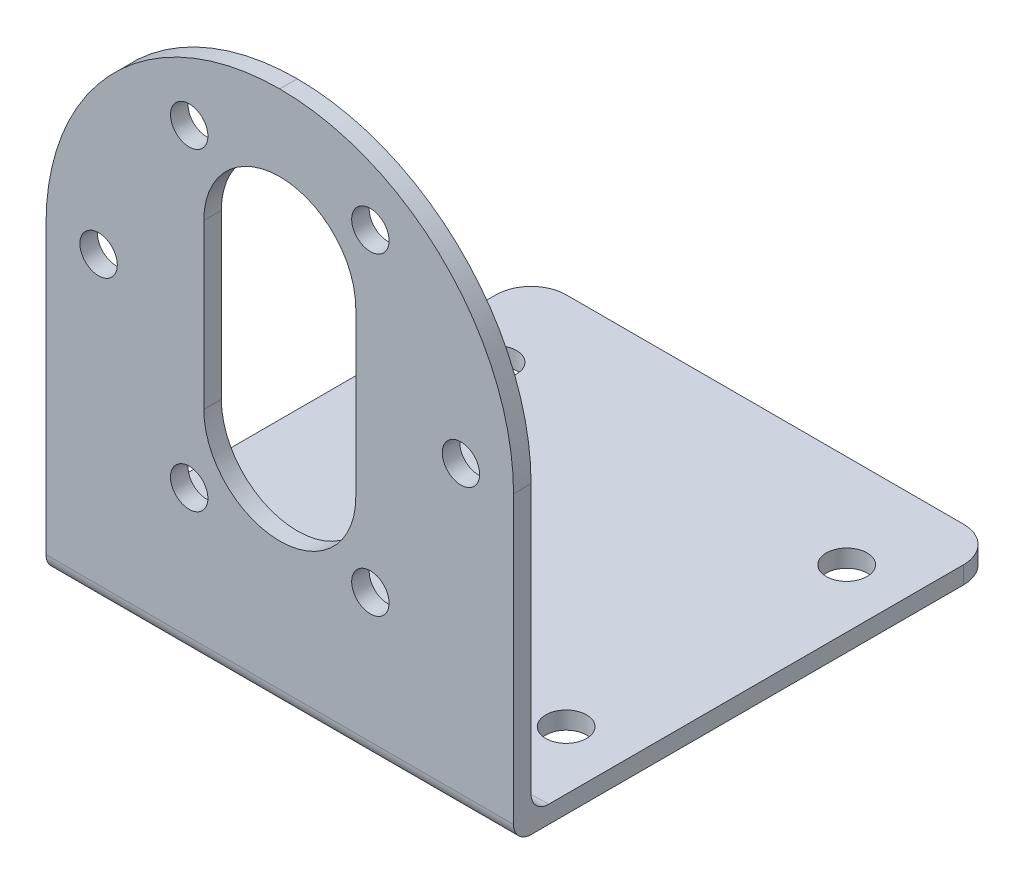
SolidWorks part; units mm, degrees
material "AISI 304"
ref_plane "前视基准面" through (0, 0, 0) normal (0, 0, 1) x (1, 0, 0)
ref_plane "上视基准面" through (0, 0, 0) normal (0, 1, 0) x (1, 0, 0)
ref_plane "右视基准面" through (0, 0, 0) normal (1, 0, 0) x (0, 0, -1)
sketch "Sketch1" plane through (0, 0, 0) normal (1, 0, 0) x (0, 0, -1)
  line L0 (0, 0) -> (40, 0)
  line L1 (40, 0) -> (40, -1.5)
  line L2 (40, -1.5) -> (-1.5, -1.5)
  line L3 (-1.5, -1.5) -> (-1.5, 44.5)
  line L4 (-1.5, 44.5) -> (0, 44.5)
  line L5 (0, 44.5) -> (0, 0)
  dimension "D1" = 1.5
  dimension "D2" = 40
  dimension "D3" = 46
extrude "Boss-Extrude1" add sketch "Sketch1" along normal blind 40
sketch "Sketch2" plane through (0, -1.5, 0) normal (0, -1, 0) x (1, 0, 0)
  line L0 (20, 1.5) -> (20, -40) construction
  line L1 (40, 1.5) -> (0, 1.5) construction
  line L2 (40, -40) -> (0, -40) construction
  circle A0 centre (5, -32) radius 1.75
  circle A1 centre (5, -8) radius 1.75
  circle A2 centre (35, -8) radius 1.75
  circle A3 centre (35, -32) radius 1.75
  dimension "D3" = 3.5
  dimension "D1" = 8
  dimension "D2" = 30
  dimension "D4" = 24
extrude "Cut-Extrude1" cut sketch "Sketch2" against normal blind 40
fillet "Fillet1" radius 3 2 edges at (40, -0.75, -40) (0, -0.75, -40)
fillet "Fillet2" radius 20 2 edges at (40, 44.5, 0.75) (0, 44.5, 0.75)
sketch "Sketch3" plane through (0, 0, 1.5) normal (0, 0, 1) x (1, 0, 0)
  line L0 (0, 24.5) -> (40, 24.5) construction
  line L1 (20, 44.5) -> (20, -1.5) construction
  line L2 (40, -1.5) -> (0, -1.5) construction
  line L3 (26.5, 31.5) -> (26.5, 17.5)
  line L4 (13.5, 31.5) -> (13.5, 17.5)
  arc A0 (26.5, 31.5) -> (13.5, 31.5) centre (20, 31.5) ccw
  arc A1 (26.5, 17.5) -> (13.5, 17.5) centre (20, 17.5) cw
  circle A2 centre (20, 24.5) radius 15.5 construction
  circle A3 centre (4.5, 24.5) radius 1.6
  circle A4 centre (12.25, 37.9234) radius 1.6
  circle A5 centre (27.75, 37.9234) radius 1.6
  circle A6 centre (35.5, 24.5) radius 1.6
  circle A7 centre (27.75, 11.0766) radius 1.6
  circle A8 centre (12.25, 11.0766) radius 1.6
  point P32 (20, 24.5)
  dimension "D2" = 13
  dimension "D3" = 31
  dimension "D4" = 3.2
  dimension "D1" = 14
  dimension "D5" = 6
extrude "Cut-Extrude2" cut sketch "Sketch3" against normal blind 40
fillet "Fillet3" radius 1.5 2 edges at (20, 0, 0) (20, -1.5, 1.5)
